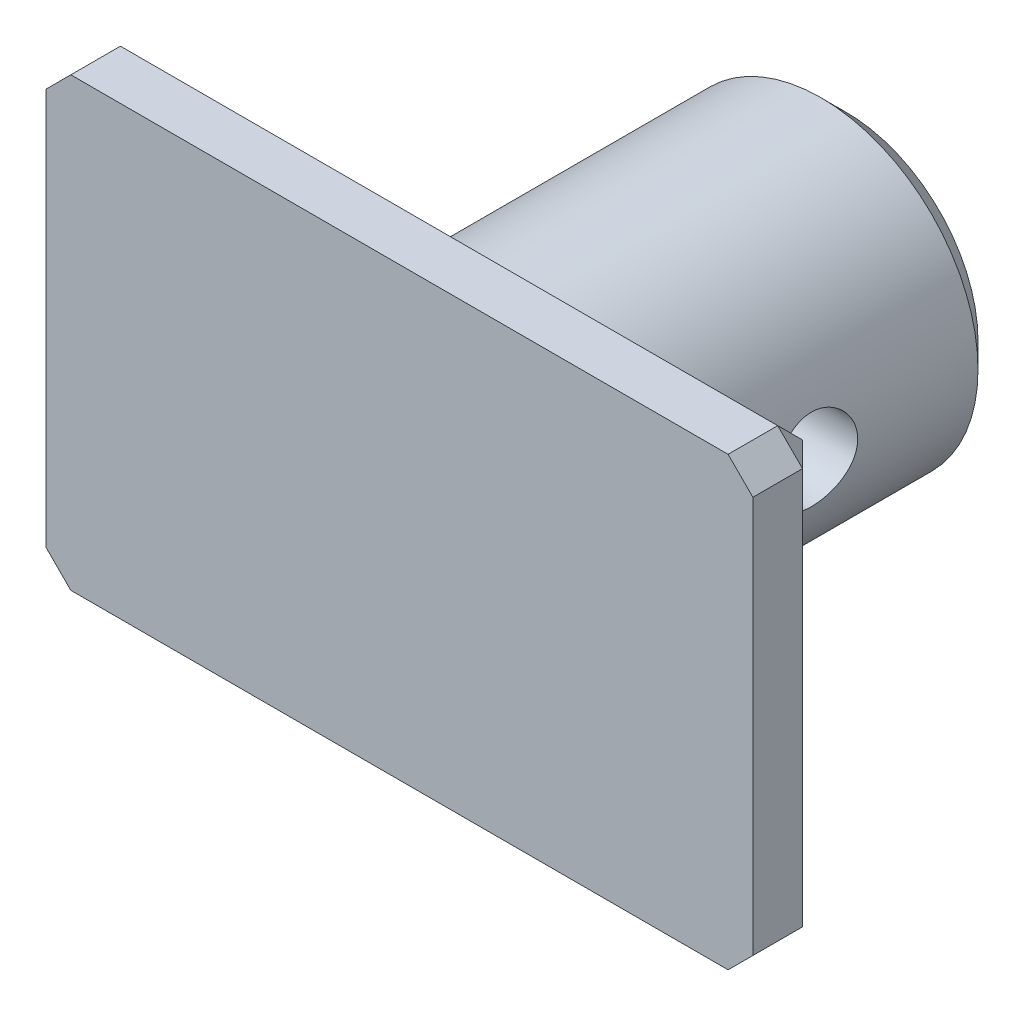
SolidWorks part; units mm, degrees
ref_plane "正面(Front)" through (0, 0, 0) normal (0, 0, 1) x (1, 0, 0)
ref_plane "平面(Top)" through (0, 0, 0) normal (0, 1, 0) x (1, 0, 0)
ref_plane "右側面(Right)" through (0, 0, 0) normal (1, 0, 0) x (0, 0, -1)
sketch "ｽｹｯﾁ1" plane through (0, 0, 0) normal (0, 0, 1) x (1, 0, 0)
  circle A0 centre (0, 0) radius 6.325
  dimension "D1" = 12.65
extrude "ﾎﾞｽ - 押し出し1" add sketch "ｽｹｯﾁ1" along normal blind 15
sketch "ｽｹｯﾁ2" plane through (0, 0, 15) normal (0, 0, 1) x (1, 0, 0)
  line L1 (-14.25, 9) -> (14.25, 9)
  line L2 (-14.25, 9) -> (-14.25, -9)
  line L3 (-14.25, -9) -> (14.25, -9)
  line L4 (14.25, 9) -> (14.25, -9)
  line L5 (-14.25, 9) -> (14.25, -9) construction
  line L6 (-14.25, -9) -> (14.25, 9) construction
  point P0 (0, 0)
  dimension "D1" = 18
  dimension "D2" = 28.5
extrude "ﾎﾞｽ - 押し出し2" add sketch "ｽｹｯﾁ2" along normal blind 3
sketch "ｽｹｯﾁ4" plane through (0, 0, 0) normal (1, 0, 0) x (0, 0, -1)
  line L0 (-18, 9) -> (-42.311, 9) construction
  line L2 (-54.0741, 13.9135) -> (-28, 9)
  line L3 (-28, 9) -> (-18, 9)
  line L5 (-18, 9) -> (-18, -9)
  line L6 (-18, -9) -> (-18, 9) construction
  line L7 (-56.6248, 4.2713) -> (-18, -9)
  line L8 (-18, -9) -> (-15, -9) construction
  arc A0 (-54.0741, 13.9135) -> (-56.6248, 4.2713) centre (-55, 9) ccw
  circle A1 centre (-55, 9) radius 1.6
  dimension "D2" = 5
  dimension "D1" = 3.2
  dimension "D3" = 37
  dimension "D4" = 10
extrude "ﾎﾞｽ - 押し出し3" add sketch "ｽｹｯﾁ4" against normal blind 7 from surface starting at face at (14.25, 0, 16.5)
extrude "ﾎﾞｽ - 押し出し4" add sketch "ｽｹｯﾁ4<2>" along normal blind 7 from surface starting at face at (-14.25, 0, 16.5)
sketch "ｽｹｯﾁ4<2>" plane through (0, 0, 0) normal (1, 0, 0) x (0, 0, -1) same geometry as "ｽｹｯﾁ4"
sketch "ｽｹｯﾁ5" plane through (-14.25, 0, 0) normal (-1, 0, 0) x (0, 0, 1)
  line L0 (18, -9) -> (33.8231, -9)
  line L1 (33.8231, -9) -> (57.5, 4.6699)
  line L2 (56.6248, 4.2713) -> (18, -9) construction
  line L3 (56.6248, 4.2713) -> (18, -9)
  arc A0 (56.6248, 4.2713) -> (54.0741, 13.9135) centre (55, 9) ccw construction
  arc A1 (56.6248, 4.2713) -> (57.5, 4.6699) centre (55, 9) ccw
  dimension "D1" = 30
extrude "ﾎﾞｽ - 押し出し5" add sketch "ｽｹｯﾁ5" against normal blind 7
mirror "ﾐﾗｰ1" about plane through (0, 0, 0) normal (1, 0, 0) of "ﾎﾞｽ - 押し出し5"
sketch "ｽｹｯﾁ7" plane through (0, 9, 0) normal (0, 1, 0) x (1, 0, 0)
  line L0 (10.75, -28) -> (10.75, -12.373) construction
  line L1 (7.25, -28) -> (14.25, -28) construction
  line L2 (7.25, -18) -> (-7.25, -18) construction
  line L3 (0, 0) -> (0, -40.3817) construction
  circle A0 centre (10.75, -23) radius 1.75
  circle A1 centre (-10.75, -23) radius 1.75
  dimension "D1" = 3.5
  dimension "D2" = 5
extrude "ｶｯﾄ - 押し出し1" cut sketch "ｽｹｯﾁ7" against normal through all
chamfer "面取り1" distance 1 angle 45 14 edges at (-14.25, -2.1651, 45.6615) (14.25, -2.1651, 45.6615) (-14.25, 10.7376, 59.6884) (14.25, 10.7376, 59.6884) (0, -9, 15) (-14.25, -9, 24.4115) (-14.25, 0, 15) (-14.25, 11.4568, 41.037) (-14.25, 9, 21.5) (0, 9, 15) (14.25, -9, 24.4115) (14.25, 0, 15) (14.25, 9, 21.5) (14.25, 11.4568, 41.037)
chamfer "面取り2" distance 1 angle 45 1 edges at (6.325, 0, 0)
sketch "ｽｹｯﾁ8" plane through (0, 0, 0) normal (1, 0, 0) x (0, 0, -1)
  line L0 (0, 0) -> (-14.2374, 0) construction
  line L1 (0, -5.325) -> (0, 5.325) construction
  circle A0 centre (-7.5, 0) radius 1.65
  dimension "D1" = 7.5
  dimension "D2" = 3.3
extrude "ｶｯﾄ - 押し出し2" cut sketch "ｽｹｯﾁ8" against normal through all both and the other way through all
sketch "ｽｹｯﾁ9" plane through (0, 9, 0) normal (0, 1, 0) x (1, 0, 0)
  line L0 (-15.3251, -18) -> (17.3145, -18)
  line L1 (7.25, -18) -> (-7.25, -18) construction
extrude "ｶｯﾄ - 押し出し3" cut sketch "ｽｹｯﾁ9" against normal through all and the other way through all flip side to cut
